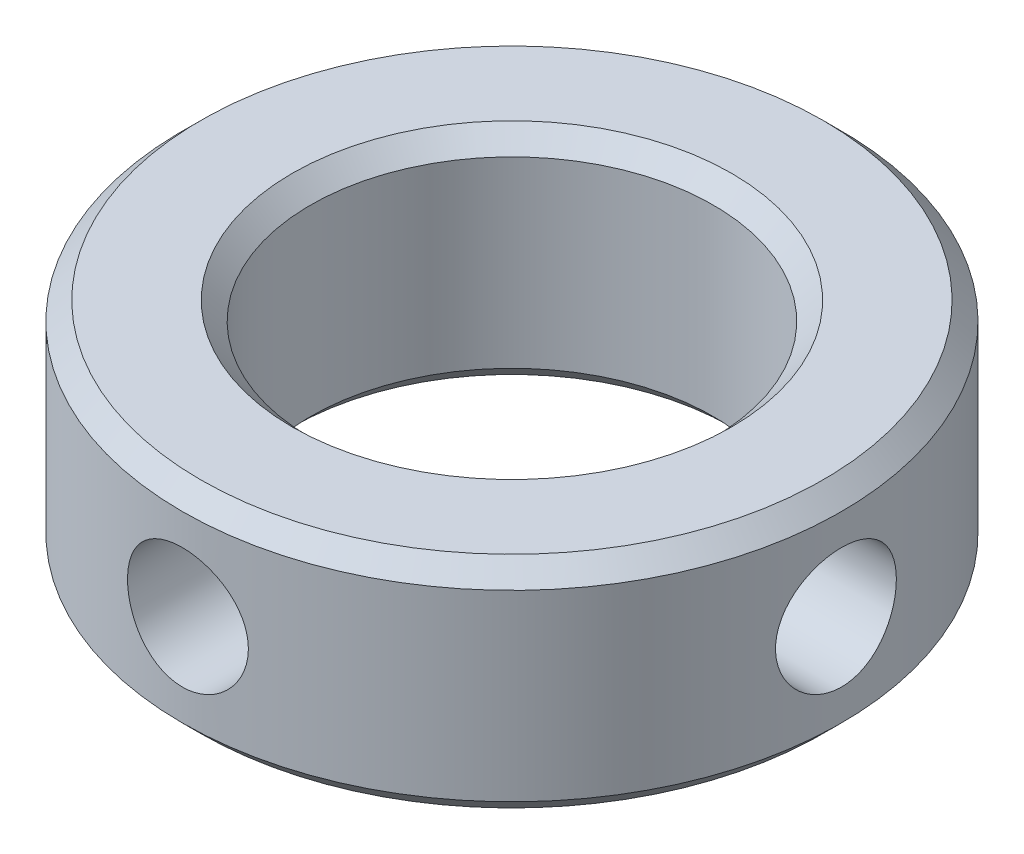
SolidWorks part; units mm, degrees
material "Aleación 1060"
ref_plane "Alzado" through (0, 0, 0) normal (0, 0, 1) x (1, 0, 0)
ref_plane "Planta" through (0, 0, 0) normal (0, 1, 0) x (1, 0, 0)
ref_plane "Vista lateral" through (0, 0, 0) normal (1, 0, 0) x (0, 0, -1)
sketch "Croquis1" plane through (0, 0, 0) normal (0, 1, 0) x (1, 0, 0)
  circle A0 centre (0, 0) radius 9
  circle A1 centre (0, 0) radius 5.5
  dimension "D1" = 18
  dimension "D2" = 11
extrude "Saliente-Extruir1" add sketch "Croquis1" along normal blind 6
ref_plane "Plano1" through (0, 0, 9) normal (0, 0, 1) x (1, 0, 0)
sketch "Croquis2" plane through (0, 0, 9) normal (0, 0, 1) x (1, 0, 0)
  line L0 (-9, 0) -> (9, 0) construction
  point P0 (0, 3)
  dimension "D1" = 3
hole_wizard "Taladro roscado M41" positions "Croquis2" profile "Croquis3" tap size "M4" standard "ISO"
sketch "Croquis3" plane through (0, 3, 9) normal (1, 0, 0) x (0, -1, 0)
  line L0 (0, 0) -> (0, 12.4914)
  line L1 (0, 12.4914) -> (1.65, 11.5)
  line L2 (1.65, 11.5) -> (1.65, 0)
  line L5 (1.65, 0) -> (0, 0)
  line L10 (0, 12.4914) -> (-1.65, 11.5) construction
  line L11 (0, -6.35) -> (0, 107.95) construction
  dimension "Diámetro de perforador para roscar" = 3.3
  dimension "Profundidad de perforador para roscar" = 11.5
  dimension "Ángulo de perforador" = 118
cosmetic thread "Rosca de taladro1" parameters "D1"=8, "D2"=4
pattern_circular "MatrizC1" count 2 every 90 about axis through (0, 0, 0) along (0, 1, 0) of "Taladro roscado M41"
cosmetic thread "Rosca de taladro2" parameters "D1"=8, "D2"=4
chamfer "Chaflán1" distance 0.5 angle 45 2 edges at (0, 6, 5.5) (0, 0, 5.5)
chamfer "Chaflán2" distance 0.5 angle 45 2 edges at (0, 6, 9) (0, 0, 9)
